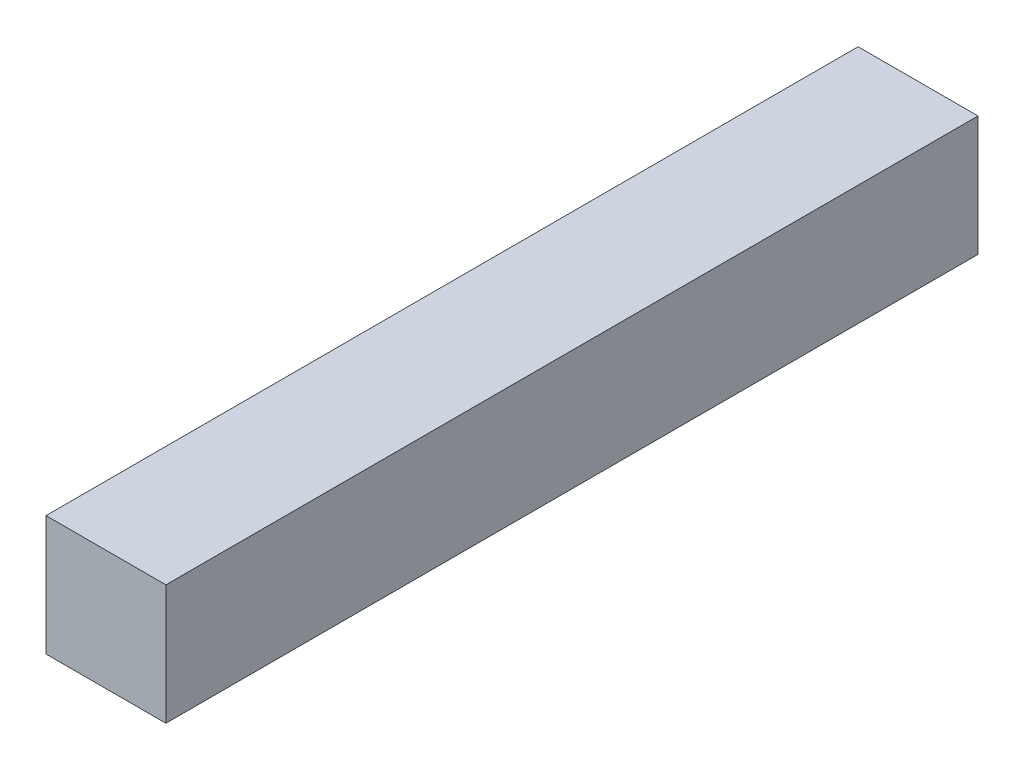
SolidWorks part; units mm, degrees
ref_plane "Front Plane" through (0, 0, 0) normal (0, 0, 1) x (1, 0, 0)
ref_plane "Top Plane" through (0, 0, 0) normal (0, 1, 0) x (1, 0, 0)
ref_plane "Right Plane" through (0, 0, 0) normal (1, 0, 0) x (0, 0, -1)
sketch "Sketch1" plane through (0, 0, 0) normal (0, 0, 1) x (1, 0, 0)
  line L1 (-15, -15) -> (15, -15)
  line L2 (-15, -15) -> (-15, 15)
  line L3 (-15, 15) -> (15, 15)
  line L4 (15, -15) -> (15, 15)
  line L5 (-15, -15) -> (15, 15) construction
  line L6 (-15, 15) -> (15, -15) construction
  point P0 (0, 0)
  dimension "D1" = 30
extrude "Boss-Extrude1" add sketch "Sketch1" along normal blind 203.2
